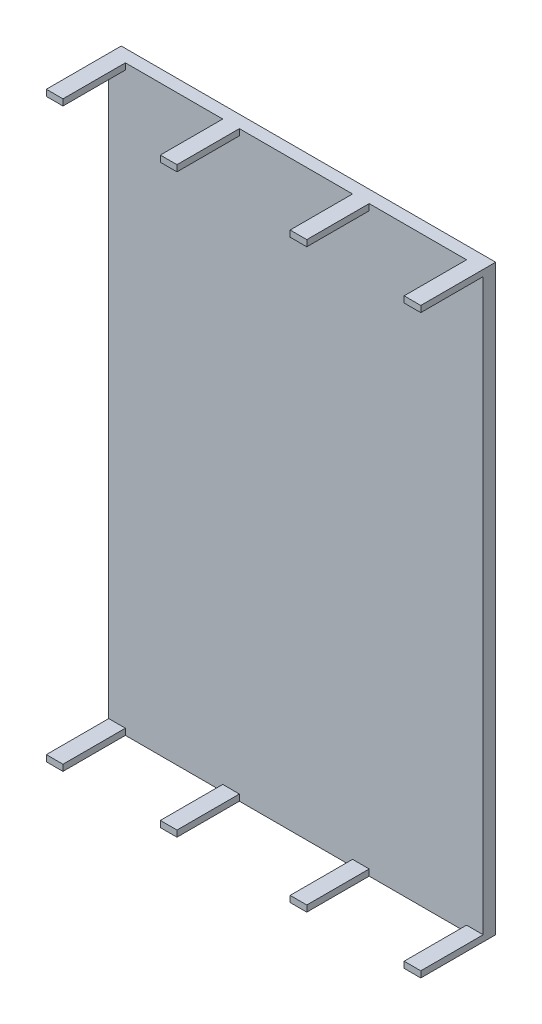
SolidWorks part; units mm, degrees
ref_plane "Front Plane" through (0, 0, 0) normal (1, 0, 0) x (0, 1, 0)
ref_plane "Top Plane" through (0, 0, 0) normal (0, 0, 1) x (0, 1, 0)
ref_plane "Right Plane" through (0, 0, 0) normal (0, 1, 0) x (-1, 0, 0)
sketch "Sketch1" plane through (0, 0, 0) normal (0, 0, 1) x (0, 1, 0)
  line L1 (0, 0) -> (-140, 0)
  line L2 (0, 0) -> (0, 90)
  line L3 (0, 90) -> (-140, 90)
  line L4 (-140, 0) -> (-140, 90)
  dimension "D1" = 90
  dimension "D2" = 140
extrude "Boss-Extrude1" add sketch "Sketch1" along normal blind 3
sketch "Sketch2" plane through (0, 0, 3) normal (0, 0, 1) x (1, 0, 0)
  line L0 (-45, 0) -> (-45, -140) construction
  line L1 (-90, 0) -> (-86, 0)
  line L2 (-90, 0) -> (-90, -1.5)
  line L3 (-90, -1.5) -> (-86, -1.5)
  line L4 (-86, 0) -> (-86, -1.5)
  line L5 (0, 0) -> (-90, 0) construction
  line L6 (-90, -140) -> (0, -140) construction
  line L7 (-90, -70) -> (0, -70) construction
  line L8 (-90, 0) -> (-90, -140) construction
  line L9 (0, -140) -> (0, 0) construction
  line L10 (0, -1.5) -> (-4, -1.5)
  line L11 (-4, 0) -> (-4, -1.5)
  line L12 (0, 0) -> (-4, 0)
  line L13 (0, 0) -> (0, -1.5)
  line L14 (0, -140) -> (0, -138.5)
  line L15 (0, -140) -> (-4, -140)
  line L16 (-4, -140) -> (-4, -138.5)
  line L17 (0, -138.5) -> (-4, -138.5)
  line L18 (-90, -138.5) -> (-86, -138.5)
  line L19 (-86, -140) -> (-86, -138.5)
  line L20 (-90, -140) -> (-86, -140)
  line L21 (-90, -140) -> (-90, -138.5)
  line L22 (-62.6, 0) -> (-58.6, 0)
  line L23 (-62.6, 0) -> (-62.6, -1.5)
  line L24 (-62.6, -1.5) -> (-58.6, -1.5)
  line L25 (-58.6, 0) -> (-58.6, -1.5)
  line L26 (-27.4, 0) -> (-27.4, -1.5)
  line L27 (-27.4, -1.5) -> (-31.4, -1.5)
  line L28 (-31.4, 0) -> (-31.4, -1.5)
  line L29 (-27.4, 0) -> (-31.4, 0)
  line L30 (-27.4, -140) -> (-31.4, -140)
  line L31 (-31.4, -140) -> (-31.4, -138.5)
  line L32 (-27.4, -138.5) -> (-31.4, -138.5)
  line L33 (-27.4, -140) -> (-27.4, -138.5)
  line L34 (-62.6, -140) -> (-62.6, -138.5)
  line L35 (-62.6, -138.5) -> (-58.6, -138.5)
  line L36 (-58.6, -140) -> (-58.6, -138.5)
  line L37 (-62.6, -140) -> (-58.6, -140)
  line M15 (0, 0) -> (-90, 0)
  line M16 (-90, 0) -> (-90, -140)
  line M17 (-90, -140) -> (0, -140)
  line M18 (0, -140) -> (0, 0)
  dimension "D1" = 1.5
  dimension "D2" = 4
  dimension "D3" = 23.4
extrude "Boss-Extrude2" add sketch "Sketch2" along normal blind 15 contours L4 L3 M15 M16 | L25 L23 L24 M15 | L28 L27 L26 M15 | L11 L10 M15 M18 | L19 L18 M17 M16 | L36 L35 L34 M17 | L32 L31 L30 L33 | L15 L16 L17 L14 region at (-88, -0.75, 3) region at (-60.6, -0.75, 3) region at (-88, -139.25, 3) region at (-29.4, -0.75, 3) region at (-60.6, -139.25, 3) region at (-2, -0.75, 3)
